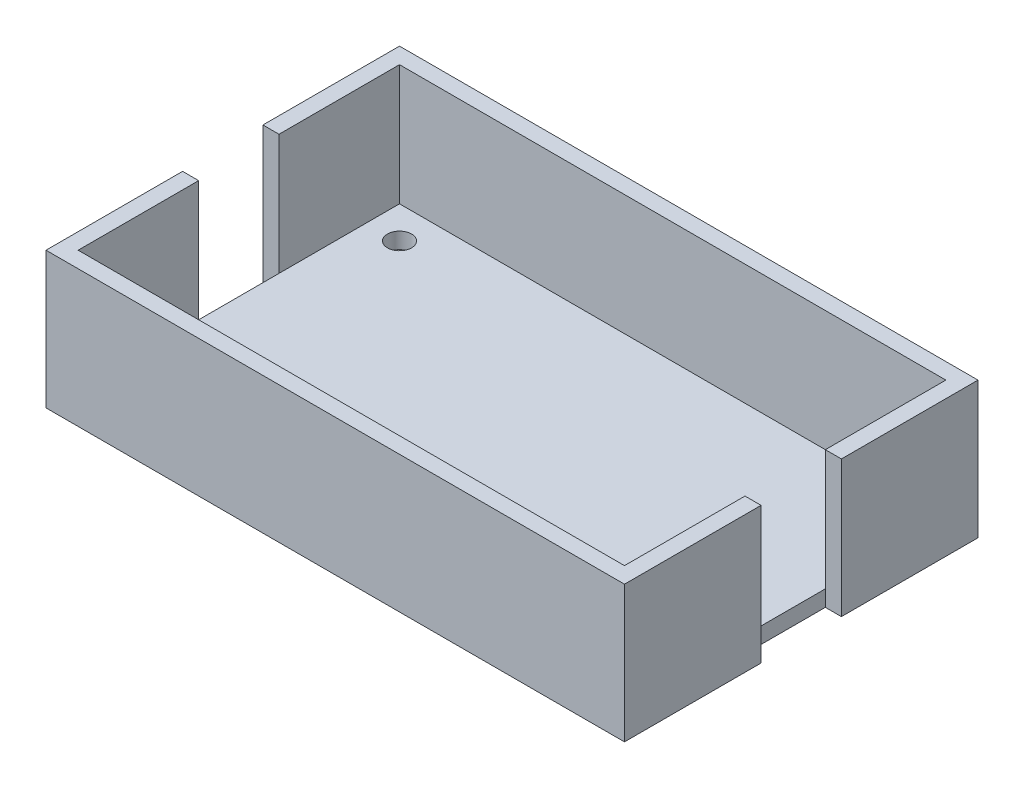
SolidWorks part; units mm, degrees
ref_plane "前视基准面" through (0, 0, 0) normal (0, 0, 1) x (1, 0, 0)
ref_plane "上视基准面" through (0, 0, 0) normal (0, 1, 0) x (1, 0, 0)
ref_plane "右视基准面" through (0, 0, 0) normal (1, 0, 0) x (0, 0, -1)
sketch "草图2" plane through (0, 0, 0) normal (0, 1, 0) x (1, 0, 0)
  line L1 (0, 0) -> (72, 0)
  line L2 (0, 0) -> (0, -44)
  line L3 (0, -44) -> (72, -44)
  line L4 (72, 0) -> (72, -44)
  line L5 (70, -42) -> (2, -42)
  line L6 (70, -42) -> (70, -2)
  line L7 (70, -2) -> (2, -2)
  line L8 (2, -42) -> (2, -2)
  circle A0 centre (66, -38) radius 1.5
  circle A1 centre (6, -38) radius 1.5
  circle A2 centre (6, -6) radius 1.5
  circle A3 centre (66, -6) radius 1.5
  dimension "D7" = 3
  dimension "D1" = 44
  dimension "D2" = 72
  dimension "D3" = 2
  dimension "D4" = 2
  dimension "D5" = 2
  dimension "D6" = 2
  dimension "D8" = 4
  dimension "D9" = 4
  dimension "D10" = 2
  dimension "D11" = 2
extrude "凸台-拉伸1" add sketch "草图2" along normal blind 15 contours L4 L1 L2 L3 L5 L8 L7 L6 region at (36, 0, 0.8438)
extrude "凸台-拉伸2" add sketch "草图2<3>" against normal blind 2 contours L8 L5 L6 L7 A3 A2 A1 A0 | L4 L1 L2 L3 L5 L8 L7 L6 region at (36, 0, 0.8438) region at (36, 0, 22)
sketch "草图2<3>" plane through (0, 0, 0) normal (0, 1, 0) x (1, 0, 0) same geometry as "草图2"
sketch "草图4" plane through (0, 0, 0) normal (-1, 0, 0) x (0, 0, 1)
  line L1 (0, 15) -> (44, 15) construction
  line L2 (17, 15) -> (27, 15)
  line L3 (17, 15) -> (17, -2)
  line L4 (17, -2) -> (27, -2)
  line L5 (27, 15) -> (27, -2)
  line L6 (0, -2) -> (44, -2) construction
  line L7 (0, 15) -> (0, -2) construction
  line L8 (44, 15) -> (44, -2) construction
  dimension "D1" = 17
  dimension "D2" = 17
extrude "切除-拉伸1" cut sketch "草图4" against normal blind 2
sketch "草图5" plane through (72, 0, 0) normal (1, 0, 0) x (0, 0, -1)
  line L0 (0, 15) -> (-44, 15) construction
  line L1 (-27, 15) -> (-17, 15)
  line L2 (-27, 15) -> (-27, -2)
  line L3 (-27, -2) -> (-17, -2)
  line L4 (-17, 15) -> (-17, -2)
  line L5 (0, -2) -> (-44, -2) construction
  line L6 (-44, 15) -> (-44, -2) construction
  line L7 (0, 15) -> (0, -2) construction
  dimension "D1" = 17
  dimension "D2" = 17
extrude "切除-拉伸2" cut sketch "草图5" against normal blind 2
